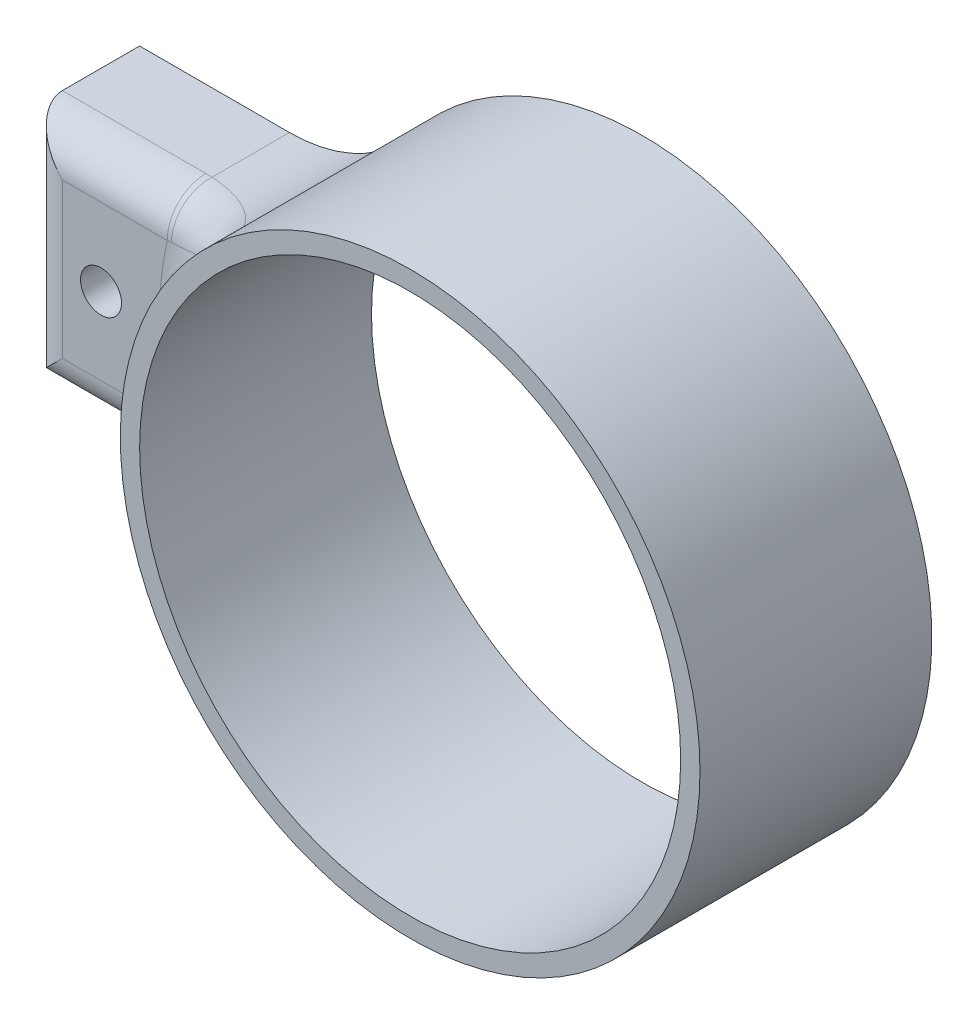
SolidWorks part; units mm, degrees
ref_plane "Plan de face" through (0, 0, 0) normal (0, 0, 1) x (1, 0, 0)
ref_plane "Plan de dessus" through (0, 0, 0) normal (0, 1, 0) x (1, 0, 0)
ref_plane "Plan de droite" through (0, 0, 0) normal (1, 0, 0) x (0, 0, -1)
sketch "Esquisse5" plane through (0, 0, 0) normal (0, 0, 1) x (1, 0, 0)
  line L0 (-1000, 0) -> (49000, 0) construction
  line L1 (-45.6207, 15) -> (-65, 15)
  line L2 (-65, 15) -> (-65, -15)
  line L3 (-45.6207, -15) -> (-65, -15)
  circle A0 centre (0, 0) radius 35
  arc A1 (-29.7526, -22.8261) -> (-29.7526, 22.8261) centre (0, 0) ccw
  arc A2 (-45.6207, 15) -> (-29.7526, 22.8261) centre (-45.6207, 35) ccw
  arc A3 (-45.6207, -15) -> (-29.7526, -22.8261) centre (-45.6207, -35) cw
  point P14 (-65, 0)
  dimension "D1" = 70
  dimension "D2" = 75
  dimension "D5" = 20
  dimension "D3" = 15
  dimension "D4" = 65
extrude "Boss.-Extru.4" add sketch "Esquisse5" along normal blind 15
sketch "Esquisse8" plane through (0, 0, 15) normal (0, 0, 1) x (1, 0, 0)
  circle A0 centre (0, 0) radius 35
  circle A1 centre (0, 0) radius 37.5
  circle A2 centre (0, 0) radius 35 construction
  arc A3 (-29.7526, -22.8261) -> (-29.7526, 22.8261) centre (0, 0) ccw construction
extrude "Boss.-Extru.7" add sketch "Esquisse8" along normal blind 15
fillet "Congé3" radius 10 1 edges at (-37.5, 0, 15)
fillet "Congé4" radius 5 7 edges at (-45.3438, 15.0019, 15) (-45.3438, -15.0019, 15) (-36.9031, 16.9999, 17.733) (-55.3104, 15, 15) (-65, 0, 15) (-55.3104, -15, 15) (-36.9031, -16.9999, 17.733)
sketch "Esquisse12" plane through (-65, 0, 0) normal (-1, 0, 0) x (0, 0, 1)
  line L5 (0, 10) -> (10, 10) construction
  line L8 (0, 15) -> (0, -15) construction
  line L9 (10, 10) -> (10, -10) construction
  line L10 (-1000, 0) -> (49000, 0) construction
  line L11 (0, -10) -> (10, -10) construction
  line L12 (10, 15) -> (0, 15) construction
  line L14 (0, 10) -> (0, -10) construction
  line L15 (-0.2, 10.2) -> (10.2, 10.2)
  line L16 (10.2, 10.2) -> (10.2, -10.2)
  line L17 (-0.2, -10.2) -> (10.2, -10.2)
  line L18 (-0.2, 10.2) -> (-0.2, -10.2)
  line L20 (15, -10) -> (15, 10) construction
  point P9 (10, 0)
  dimension "D1" = 5
  dimension "D2" = 5
  dimension "D3" = 0.2
extrude "Enlèv. mat.-Extru.2" cut sketch "Esquisse12" against normal blind 25
sketch "Esquisse13" plane through (0, 0, 15) normal (0, 0, 1) x (1, 0, 0)
  line L0 (-64.996, -10.2) -> (-64.996, 10.2) construction
  circle A0 centre (-54.996, 0) radius 2.65
  dimension "D1" = 5.3
  dimension "D2" = 10
extrude "Enlèv. mat.-Extru.3" cut sketch "Esquisse13" against normal up to next and the other way through all
